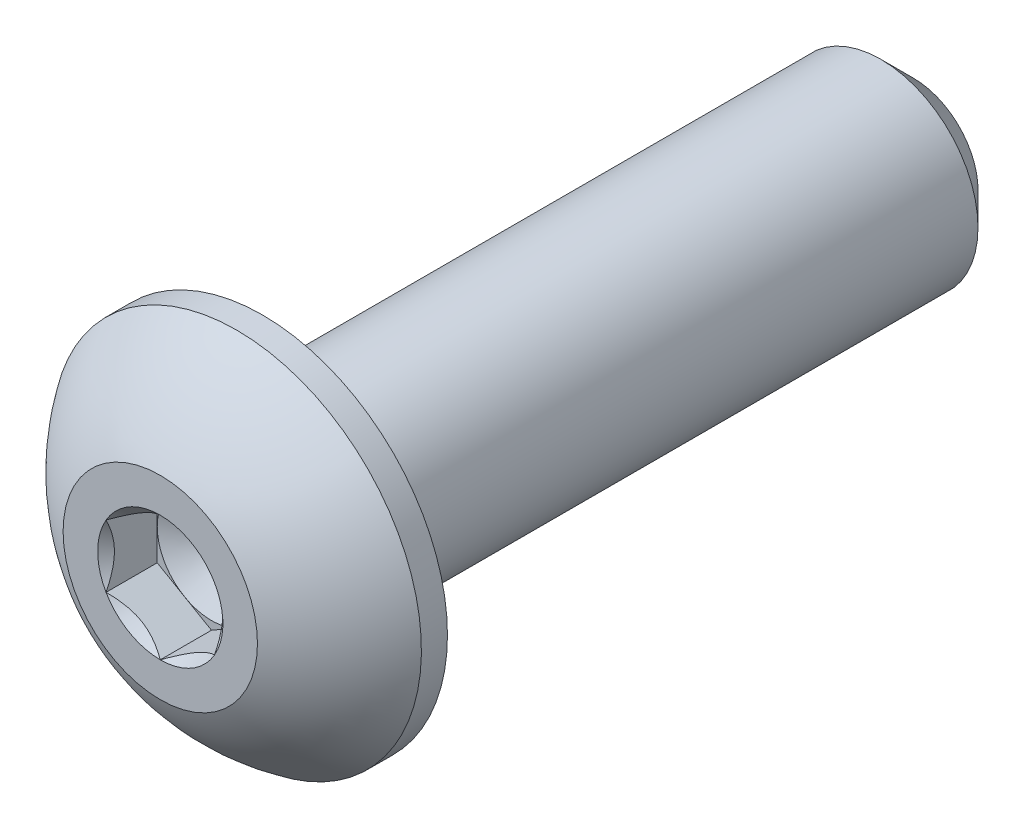
SolidWorks part; units mm, degrees
ref_plane "Front" through (0, 0, 0) normal (0, 0, 1) x (1, 0, 0)
ref_plane "Top" through (0, 0, 0) normal (0, 1, 0) x (1, 0, 0)
ref_plane "Right" through (0, 0, 0) normal (1, 0, 0) x (0, 0, -1)
sketch "Sketch1" plane through (0, 0, 0) normal (1, 0, 0) x (0, 0, -1)
  line L0 (0, 0) -> (-1.4986, 0) construction
  line L1 (0, 0) -> (9.525, 0)
  line L2 (0, 0) -> (0, 1.4224)
  line L3 (0, 1.4224) -> (9.525, 1.4224)
  line L4 (9.525, 0) -> (9.525, 1.4224)
  line L5 (0, -1.4224) -> (9.525, -1.4224) construction
  dimension "D1" = 9.525
  dimension "Thread Dia" = 2.8448
  dimension "Length" = 9.525
  dimension "Head Height" = 1.4986
revolve "Revolve1" add sketch "Sketch1" angle 360 about L0
ref_plane "Plane1" through (0, 0, 1.4986) normal (0, 0, 1) x (1, 0, 0)
chamfer "Chamfer1" distance 0.4763 angle 45 1 edges at (0, 1.4224, -9.525)
sketch "Sketch10" plane through (0, 0, 0) normal (1, 0, 0) x (0, 0, -1)
  line L0 (9.525, 1.4224) -> (10.0806, 1.4224)
  line L1 (10.0806, 1.4224) -> (9.8425, 1.01)
  line L2 (9.8425, 1.01) -> (9.7631, 1.01)
  line L3 (9.7631, 1.01) -> (9.525, 1.4224)
  line L4 (9.6441, 1.2162) -> (9.9616, 1.2162) construction
  dimension "D1" = 60
  dimension "D2" = 0.0794
  dimension "D3" = 0.3175
sketch "Sketch11" plane through (0, 0, -9.525) normal (0, 0, -1) x (-1, 0, 0)
  circle A1 centre (0, 0) radius 0.9462
  circle A2 centre (0, 0) radius 0.9462
  dimension "D1" = 0
curve "Helix/Spiral1" pitch 0.635 height 12.7 turns 20
sweep "Cut-Sweep1" [suppressed] cut profiles "Sketch10" path "Helix/Spiral1"
sketch "Sketch4" plane through (0, 0, 0) normal (0, 0, 1) x (1, 0, 0)
  circle A0 centre (0, 0) radius 2.7051
  dimension "Head Dia" = 5.4102
extrude "Extrude1" add sketch "Sketch4" along normal up to surface (1.4986 mm away) up to plane "Plane1"
sketch "Sketch9" plane through (0, 0, 0) normal (1, 0, 0) x (0, 0, -1)
  line L0 (0, 2.7051) -> (-0.381, 2.7051)
  line L1 (0, 2.7051) -> (0, 3.0861)
  line L2 (0, 3.0861) -> (-1.8796, 3.0861)
  line L3 (0, 0) -> (-1.4986, 0) construction
  line L4 (-1.8796, 3.0861) -> (-1.8796, 1.4224)
  line L5 (-1.8796, 1.4224) -> (-1.4986, 1.4224)
  line L6 (0, 0) -> (0, 1.4224) construction
  line L10 (0, 2.7051) -> (-1.4986, 2.7051) construction
  line L11 (0, 1.4224) -> (9.525, 1.4224) construction
  line L12 (-1.4986, 2.7051) -> (-1.4986, -2.7051) construction
  arc A0 (-1.4986, 1.4224) -> (-0.381, 2.7051) centre (1.4288, 0) cw
  dimension "Side Head Height" = 0.381
revolve "Cut-Revolve3" cut sketch "Sketch9" angle 360 about L3
sketch "Sketch6" plane through (0, 0, 1.4986) normal (0, 0, 1) x (1, 0, 0)
  line L1 (0, -0.9165) -> (0.7937, -0.4583)
  line L2 (0.7937, -0.4583) -> (0.7937, 0.4583)
  line L3 (0.7937, 0.4583) -> (0, 0.9165)
  line L4 (0, 0.9165) -> (-0.7938, 0.4583)
  line L5 (-0.7938, 0.4583) -> (-0.7938, -0.4583)
  line L6 (-0.7938, -0.4583) -> (0, -0.9165)
  circle A0 centre (0, 0) radius 0.7938 construction
  dimension "Hex" = 1.5875
extrude "Cut-Extrude1" cut sketch "Sketch6" against normal blind 0.7493
sketch "Sketch7" plane through (0, 0, 1.4986) normal (0, 0, 1) x (1, 0, 0)
  circle A0 centre (0, 0) radius 0.9165
extrude "Cut-Extrude4" cut sketch "Sketch7" against normal blind 0.7493 draft 45
sketch "Sketch8" plane through (0, 0, 0.7493) normal (0, 0, 1) x (1, 0, 0)
  circle A0 centre (0, 0) radius 0.7938 construction
  circle A1 centre (0, 0) radius 0.7938
extrude "Cut-Extrude5" cut sketch "Sketch8" against normal blind 0.2498 draft 60
sketch "Sketch12" [suppressed] plane through (0, 0, 0) normal (1, 0, 0) x (0, 0, -1)
  line L1 (0, -1.4224) -> (9.525, -1.4224) construction
  spline S0 degree 2 poles (9.0487, 0.013) (9.0069, 0.5945) (8.9694, 1.0058) (8.9165, 1.5865) (8.8635, 1.3739) (8.8106, 1.1614) (8.7577, 0.3681) (8.7048, -0.4251) (8.6519, -1.0058) (8.599, -1.5865) (8.546, -1.3739) (8.4931, -1.1614) (8.4402, -0.3681) (8.3873, 0.4251) (8.3344, 1.0058) (8.2815, 1.5865) (8.2285, 1.3739) (8.1756, 1.1614) (8.1227, 0.3681) (8.0698, -0.4251) (8.0169, -1.0058) (7.964, -1.5865) (7.911, -1.3739) (7.8581, -1.1614) (7.8052, -0.3681) (7.7523, 0.4251) (7.6994, 1.0058) (7.6465, 1.5865) (7.5935, 1.3739) (7.5406, 1.1614) (7.4877, 0.3681) (7.4348, -0.4251) (7.3819, -1.0058) (7.329, -1.5865) (7.276, -1.3739) (7.2231, -1.1614) (7.1702, -0.3681) (7.1173, 0.4251) (7.0644, 1.0058) (7.0115, 1.5865) (6.9585, 1.3739) (6.9056, 1.1614) (6.8527, 0.3681) (6.7998, -0.4251) (6.7469, -1.0058) (6.694, -1.5865) (6.641, -1.3739) (6.5881, -1.1614) (6.5352, -0.3681) (6.4823, 0.4251) (6.4294, 1.0058) (6.3765, 1.5865) (6.3235, 1.3739) (6.2706, 1.1614) (6.2177, 0.3681) (6.1648, -0.4251) (6.1119, -1.0058) (6.059, -1.5865) (6.006, -1.3739) (5.9531, -1.1614) (5.9002, -0.3681) (5.8473, 0.4251) (5.7944, 1.0058) (5.7415, 1.5865) (5.6885, 1.3739) (5.6356, 1.1614) (5.5827, 0.3681) (5.5298, -0.4251) (5.4769, -1.0058) (5.424, -1.5865) (5.371, -1.3739) (5.3181, -1.1614) (5.2652, -0.3681) (5.2123, 0.4251) (5.1594, 1.0058) (5.1065, 1.5865) (5.0535, 1.3739) (5.0006, 1.1614) (4.9477, 0.3681) (4.8948, -0.4251) (4.8419, -1.0058) (4.789, -1.5865) (4.736, -1.3739) (4.6831, -1.1614) (4.6302, -0.3681) (4.5773, 0.4251) (4.5244, 1.0058) (4.4715, 1.5865) (4.4185, 1.3739) (4.3656, 1.1614) (4.3127, 0.3681) (4.2598, -0.4251) (4.2069, -1.0058) (4.154, -1.5865) (4.101, -1.3739) (4.0481, -1.1614) (3.9952, -0.3681) (3.9423, 0.4251) (3.8894, 1.0058) (3.8365, 1.5865) (3.7835, 1.3739) (3.7306, 1.1614) (3.6777, 0.3681) (3.6248, -0.4251) (3.5719, -1.0058) (3.519, -1.5865) (3.466, -1.3739) (3.4131, -1.1614) (3.3602, -0.3681) (3.3073, 0.4251) (3.2544, 1.0058) (3.2015, 1.5865) (3.1485, 1.3739) (3.0956, 1.1614) (3.0427, 0.3681) (2.9898, -0.4251) (2.9369, -1.0058) (2.884, -1.5865) (2.831, -1.3739) (2.7781, -1.1614) (2.7252, -0.3681) (2.6723, 0.4251) (2.6194, 1.0058) (2.5665, 1.5865) (2.5135, 1.3739) (2.4606, 1.1614) (2.4077, 0.3681) (2.3548, -0.4251) (2.3019, -1.0058) (2.249, -1.5865) (2.196, -1.3739) (2.1431, -1.1614) (2.0902, -0.3681) (2.0373, 0.4251) (1.9844, 1.0058) (1.9315, 1.5865) (1.8785, 1.3739) (1.8256, 1.1614) (1.7727, 0.3681) (1.7198, -0.4251) (1.6669, -1.0058) (1.614, -1.5865) (1.561, -1.3739) (1.5081, -1.1614) (1.4552, -0.3681) (1.4023, 0.4251) (1.3494, 1.0058) (1.2965, 1.5865) (1.2435, 1.3739) (1.1906, 1.1614) (1.1377, 0.3681) (1.0848, -0.4251) (1.0319, -1.0058) (0.979, -1.5865) (0.926, -1.3739) (0.8731, -1.1614) (0.8202, -0.3681) (0.7673, 0.4251) (0.7144, 1.0058) (0.6615, 1.5865) (0.6085, 1.3739) (0.5556, 1.1614) (0.5027, 0.3681) (0.4498, -0.4251) (0.3969, -1.0058) (0.344, -1.5865) (0.291, -1.3739) (0.2381, -1.1614) (0.1852, -0.3681) (0.1323, 0.4251) (0.0794, 1.0058) (0.0419, 1.417) (0, 1.4223) knots 0.043858 0.043858 0.043858 0.05 0.05 0.058333 0.058333 0.066667 0.066667 0.075 0.075 0.083333 0.083333 0.091667 0.091667 0.1 0.1 0.108333 0.108333 0.116667 0.116667 0.125 0.125 0.133333 0.133333 0.141667 0.141667 0.15 0.15 0.158333 0.158333 0.166667 0.166667 0.175 0.175 0.183333 0.183333 0.191667 0.191667 0.2 0.2 0.208333 0.208333 0.216667 0.216667 0.225 0.225 0.233333 0.233333 0.241667 0.241667 0.25 0.25 0.258333 0.258333 0.266667 0.266667 0.275 0.275 0.283333 0.283333 0.291667 0.291667 0.3 0.3 0.308333 0.308333 0.316667 0.316667 0.325 0.325 0.333333 0.333333 0.341667 0.341667 0.35 0.35 0.358333 0.358333 0.366667 0.366667 0.375 0.375 0.383333 0.383333 0.391667 0.391667 0.4 0.4 0.408333 0.408333 0.416667 0.416667 0.425 0.425 0.433333 0.433333 0.441667 0.441667 0.45 0.45 0.458333 0.458333 0.466667 0.466667 0.475 0.475 0.483333 0.483333 0.491667 0.491667 0.5 0.5 0.508333 0.508333 0.516667 0.516667 0.525 0.525 0.533333 0.533333 0.541667 0.541667 0.55 0.55 0.558333 0.558333 0.566667 0.566667 0.575 0.575 0.583333 0.583333 0.591667 0.591667 0.6 0.6 0.608333 0.608333 0.616667 0.616667 0.625 0.625 0.633333 0.633333 0.641667 0.641667 0.65 0.65 0.658333 0.658333 0.666667 0.666667 0.675 0.675 0.683333 0.683333 0.691667 0.691667 0.7 0.7 0.708333 0.708333 0.716667 0.716667 0.725 0.725 0.733333 0.733333 0.741667 0.741667 0.75 0.75 0.756142 0.756142 0.756142 weights 0.948065 0.901259 1 0.866025 1 0.866025 1 0.866025 1 0.866025 1 0.866025 1 0.866025 1 0.866025 1 0.866025 1 0.866025 1 0.866025 1 0.866025 1 0.866025 1 0.866025 1 0.866025 1 0.866025 1 0.866025 1 0.866025 1 0.866025 1 0.866025 1 0.866025 1 0.866025 1 0.866025 1 0.866025 1 0.866025 1 0.866025 1 0.866025 1 0.866025 1 0.866025 1 0.866025 1 0.866025 1 0.866025 1 0.866025 1 0.866025 1 0.866025 1 0.866025 1 0.866025 1 0.866025 1 0.866025 1 0.866025 1 0.866025 1 0.866025 1 0.866025 1 0.866025 1 0.866025 1 0.866025 1 0.866025 1 0.866025 1 0.866025 1 0.866025 1 0.866025 1 0.866025 1 0.866025 1 0.866025 1 0.866025 1 0.866025 1 0.866025 1 0.866025 1 0.866025 1 0.866025 1 0.866025 1 0.866025 1 0.866025 1 0.866025 1 0.866025 1 0.866025 1 0.866025 1 0.866025 1 0.866025 1 0.866025 1 0.866025 1 0.866025 1 0.866025 1 0.866025 1 0.866025 1 0.866025 1 0.866025 1 0.866025 1 0.866025 1 0.866025 1 0.866025 1 0.866025 1 0.866025 1 0.866025 1 0.866025 1 0.901259 0.948065 construction
  point P0 (8.5716, -1.4224)
equation "\"D1@Cut-Extrude1\"=\"Head Height@Sketch1\"/2"
equation "\"D1@Cut-Extrude4\"=\"D1@Cut-Extrude1\""
equation "\"D1@Cut-Extrude5\"=\"D1@Cut-Extrude1\"/3"
equation "\"D3@Helix/Spiral1\" = \"Length@Sketch1\" + .125"
equation "\"D1@Chamfer1\" = \"D4@Helix/Spiral1\" * .75"
equation "\"D2@Sketch10\" = \"D4@Helix/Spiral1\" * .125"
equation "\"D3@Sketch10\" = \"D4@Helix/Spiral1\" * .5"
